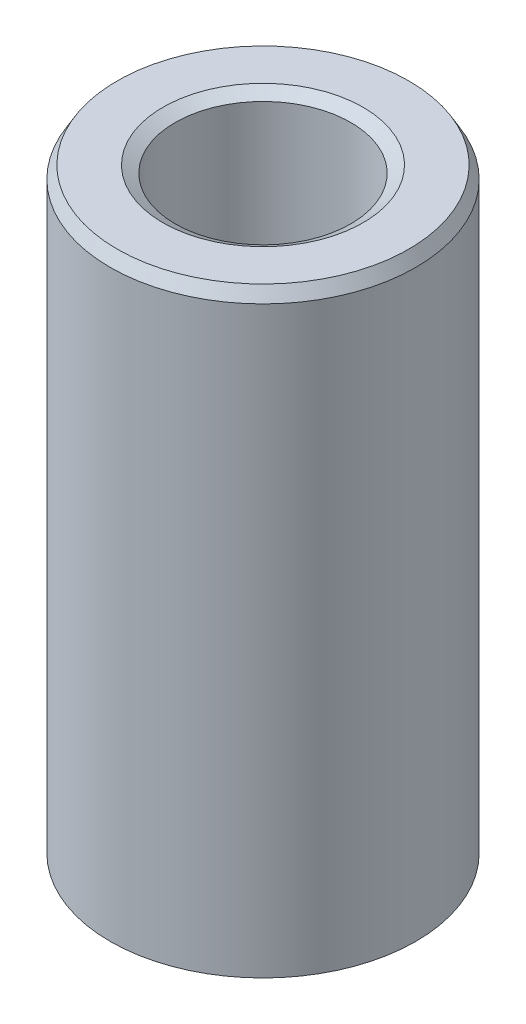
SolidWorks part; units mm, degrees
ref_plane "Front Plane" through (0, 0, 0) normal (0, 0, 1) x (1, 0, 0)
ref_plane "Top Plane" through (0, 0, 0) normal (0, 1, 0) x (1, 0, 0)
ref_plane "Right Plane" through (0, 0, 0) normal (1, 0, 0) x (0, 0, -1)
sketch "Sketch1" plane through (0, 0, 0) normal (0, 1, 0) x (1, 0, 0)
  circle A0 centre (0, 0) radius 35
  dimension "SLEEVE_OD" = 70
extrude "Boss-Extrude1" add sketch "Sketch1" along normal blind 138.0929
sketch "Sketch2" plane through (0, 0, 0) normal (0, 1, 0) x (1, 0, 0)
  circle A0 centre (0, 0) radius 20.114
  dimension "BORE_D" = 40.2281
extrude "Cut-Extrude1" cut sketch "Sketch2" along normal through all
chamfer "Chamfer1" distance 2.8053 angle 30 4 edges at (0, 138.0929, 20.114) (0, 0, 20.114) (0, 0, 35) (0, 138.0929, 35) first distance on face at (0, 138.0929, 20.114) first distance on face at (0, 0, 20.114) first distance on face at (0, 138.0929, 35)
